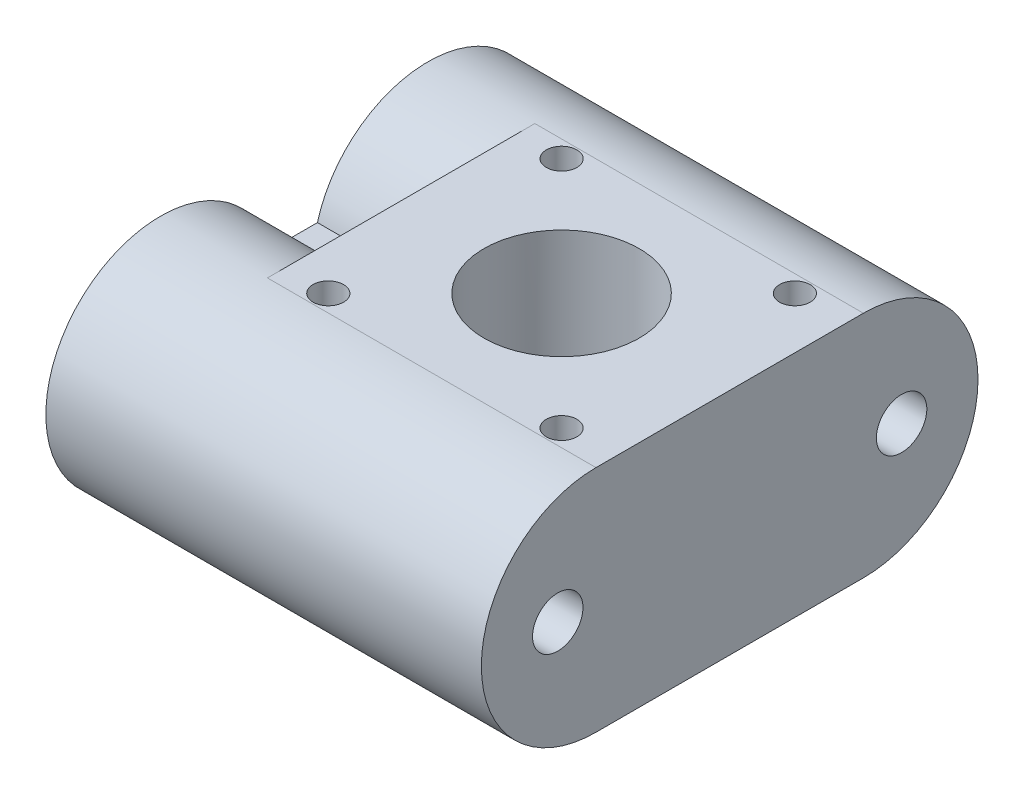
SolidWorks part; units mm, degrees
ref_plane "Front Plane" through (0, 0, 0) normal (0, 0, 1) x (1, 0, 0)
ref_plane "Top Plane" through (0, 0, 0) normal (0, 1, 0) x (1, 0, 0)
ref_plane "Right Plane" through (0, 0, 0) normal (1, 0, 0) x (0, 0, -1)
sketch "Sketch1" plane through (0, 0, 0) normal (0, 1, 0) x (1, 0, 0)
  line L1 (-17.5, -16.25) -> (17.5, -16.25)
  line L2 (-17.5, -16.25) -> (-17.5, 16.25)
  line L3 (-17.5, 16.25) -> (17.5, 16.25)
  line L4 (17.5, -16.25) -> (17.5, 16.25)
  line L5 (-17.5, -16.25) -> (17.5, 16.25) construction
  line L6 (-17.5, 16.25) -> (17.5, -16.25) construction
  point P0 (0, 0)
  dimension "D1" = 35
  dimension "D2" = 32.5
extrude "Boss-Extrude1" add sketch "Sketch1" against normal blind 15
sketch "Sketch2" plane through (0, 0, 0) normal (0, 1, 0) x (1, 0, 0)
  circle A0 centre (0, 0) radius 5.08
  dimension "D2" = 10.16
extrude "Cut-Extrude2" cut sketch "Sketch2" against normal blind 30
sketch "Sketch4" plane through (0, 0, 0) normal (0, 1, 0) x (1, 0, 0)
  line L0 (7.633, 7.633) -> (7.633, 0) construction
  line L1 (7.633, 0) -> (0, 0) construction
  line L2 (0, 0) -> (-7.633, 0) construction
  line L3 (-7.633, 0) -> (-7.633, 7.633) construction
  line L4 (7.633, 0) -> (7.633, -7.633) construction
  line L5 (-7.633, 0) -> (-7.633, -7.633) construction
  circle A0 centre (7.633, 7.633) radius 1
  circle A1 centre (-7.633, 7.633) radius 1
  circle A2 centre (-7.633, -7.633) radius 1
  circle A3 centre (7.633, -7.633) radius 1
  dimension "D2" = 2
  dimension "D1" = 7.633
extrude "Cut-Extrude3" cut sketch "Sketch4" against normal blind 15
hole_wizard "M4x0.7 Tapped Hole1" positions "Sketch6" profile "Sketch5" tap size "M4x0.7" standard "ANSI Metric" end condition through all
sketch "Sketch6" plane through (-17.5, 0, 0) normal (1, 0, 0) x (0, -1, 0)
  line L1 (7.5, 16.25) -> (7.5, -16.25) construction
  line L2 (15, 16.25) -> (0, 16.25) construction
  line L3 (15, -16.25) -> (0, -16.25) construction
  point P0 (7.5, 11.25)
  point P2 (7.5, -11.25)
  dimension "D1" = 5
  dimension "D2" = 5
sketch "Sketch5" plane through (-17.5, -7.5, -11.25) normal (0, 1, 0) x (0, 0, 1)
  line L0 (0, 0) -> (0, 35)
  line L1 (0, 35) -> (1.65, 35)
  line L2 (1.65, 35) -> (1.65, 0)
  line L5 (1.65, 0) -> (0, 0)
  line L11 (0, -6.35) -> (0, 107.95) construction
  dimension "Thru Tap Drill Dia." = 3.3
  dimension "Thru Tap Drill Depth" = 35
cosmetic thread "Hole Thread1" parameters "D2"=4
cosmetic thread "Hole Thread2" parameters "D2"=4
fillet "Fillet1" 2 edges at (0, -15, -16.25) (0, 0, -16.25) type full round first side face at (7.633, -15, 8.633) second side face at (7.633, 0, 8.633) middle face at (0, -7.5, -16.25)
fillet "Fillet2" 2 edges at (0, 0, 16.25) (0, -15, 16.25) type full round first side face at (7.633, 0, 8.633) second side face at (7.633, -15, 8.633) middle face at (0, -7.5, 16.25)
sketch "Sketch19" plane through (0, -15, 0) normal (0, -1, 0) x (1, 0, 0)
  line L0 (-17.5, -16.25) -> (17.5, -16.25) construction
  line L1 (17.5, 16.25) -> (11, 16.25)
  line L2 (17.5, 16.25) -> (17.5, -16.25)
  line L3 (17.5, -16.25) -> (11, -16.25)
  line L4 (11, 16.25) -> (11, -16.25)
  line L5 (14.25, -16.25) -> (14.25, 16.25) construction
  line L6 (17.5, 0) -> (11, 0) construction
  point P152 (14.25, 0)
  dimension "D1" = 11
extrude "Cut-Extrude13" cut sketch "Sketch19" against normal through all
sketch "Sketch20" plane through (-17.5, 0, 0) normal (-1, 0, 0) x (0, 0, 1)
  line L1 (-1.5216, -9.5) -> (1.5216, -9.5)
  line L2 (-1.5216, -9.5) -> (-1.5216, -5.5)
  line L3 (-1.5216, -5.5) -> (1.5216, -5.5)
  line L4 (1.5216, -9.5) -> (1.5216, -5.5)
  line L5 (0, -5.5) -> (0, -9.5) construction
  line L6 (-1.5216, -7.5) -> (1.5216, -7.5) construction
  circle A0 centre (-8.75, -7.5) radius 7.5
  circle A1 centre (8.75, -7.5) radius 7.5
  arc A3 (-8.75, 0) -> (-8.75, -15) centre (-8.75, -7.5) ccw construction
  point P12 (0, 0)
  point P13 (2.9393, -12.2419)
  point P100 (0, -7.5)
  circle M5 centre (-11.25, -7.5) radius 1.65
  circle M6 centre (11.25, -7.5) radius 1.65
  line M7 (-8.75, -15) -> (8.75, -15)
  arc M8 (8.75, -15) -> (8.75, 0) centre (8.75, -7.5) ccw
  line M9 (8.75, 0) -> (-8.75, 0)
  arc M10 (-8.75, 0) -> (-8.75, -15) centre (-8.75, -7.5) ccw
  dimension "D1" = 4
extrude "Cut-Extrude14" cut sketch "Sketch20" against normal blind 7 flip side to cut contours L2 A0 M9 M10 M7 M5 | A1 L3 A0 L1 | L2 A0 | L4 A1 | A1 L4 M8 M6 region at (-17.5, -7.5, 0) region at (-17.5, -7.5, -8.6541) region at (-17.5, -7.5, -1.4128) region at (-17.5, -7.5, 1.4128) region at (-17.5, -7.5, 8.6541)
